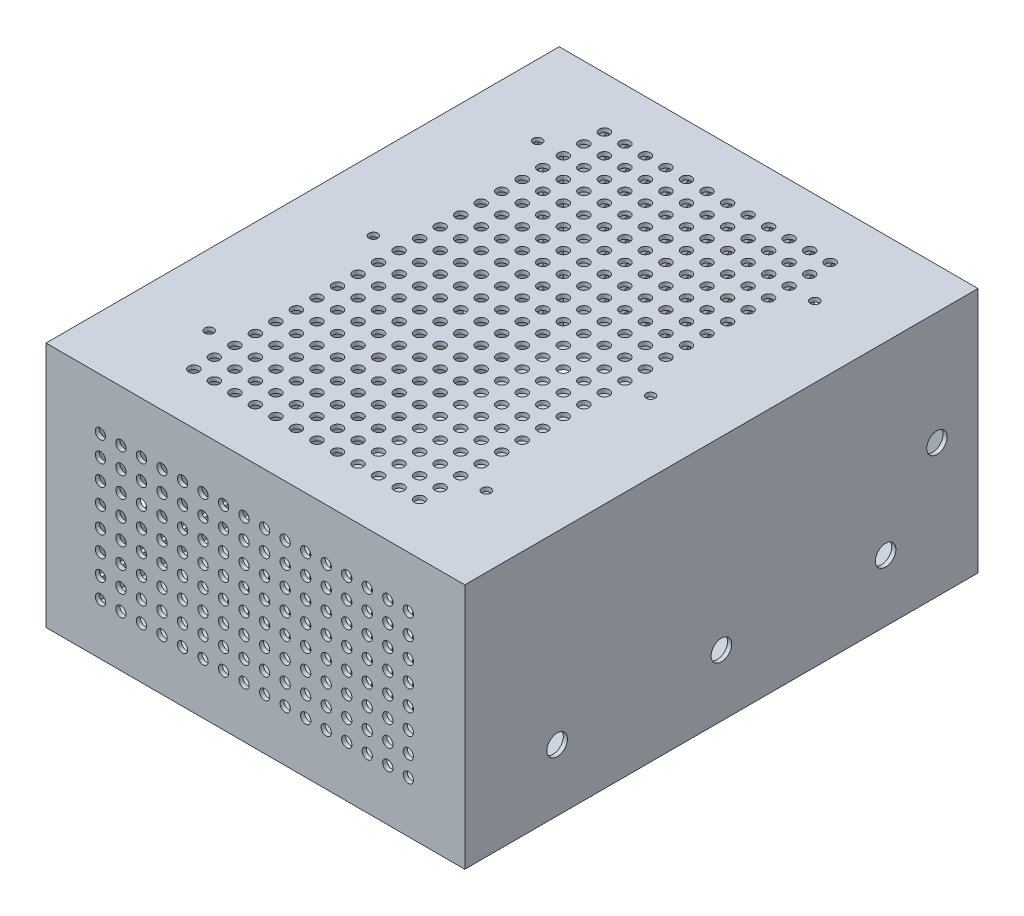
SolidWorks part; units mm, degrees
ref_plane "Alzado" through (0, 0, 0) normal (0, 0, 1) x (1, 0, 0)
ref_plane "Planta" through (0, 0, 0) normal (0, 1, 0) x (1, 0, 0)
ref_plane "Vista lateral" through (0, 0, 0) normal (1, 0, 0) x (0, 0, -1)
sketch "Croquis1" plane through (0, 0, 0) normal (0, 0, 1) x (1, 0, 0)
  line L0 (-100, 0) -> (100, 0)
  line L1 (100, 0) -> (100, 116)
  line L2 (100, 116) -> (-100, 116)
  line L3 (-100, 116) -> (-100, 0)
  line L4 (-80, 96) -> (-80, 20)
  line L5 (-80, 20) -> (80, 20)
  line L6 (80, 20) -> (80, 96)
  line L7 (80, 96) -> (-80, 96)
  point P3 (0, 0)
  dimension "D1" = 116
  dimension "D2" = 200
  dimension "D3" = 20
  dimension "D4" = 20
  dimension "D5" = 20
  dimension "D6" = 20
extrude "Saliente-Extruir1" add sketch "Croquis1" against normal blind 2
sketch "Croquis2" plane through (0, 0, 0) normal (0, 0, 1) x (1, 0, 0)
  line L0 (-80, 96) -> (-80, 20)
  line L1 (-80, 20) -> (80, 20)
  line L3 (80, 20) -> (80, 96)
  line L4 (80, 96) -> (-80, 96)
  circle A0 centre (-75.5, 93) radius 2.5
  circle A1 centre (-65.5, 93) radius 2.5
  circle A2 centre (-55.5, 93) radius 2.5
  circle A3 centre (-45.5, 93) radius 2.5
  circle A4 centre (-35.5, 93) radius 2.5
  circle A5 centre (-25.5, 93) radius 2.5
  circle A6 centre (-15.5, 93) radius 2.5
  circle A7 centre (-5.5, 93) radius 2.5
  circle A8 centre (4.5, 93) radius 2.5
  circle A9 centre (14.5, 93) radius 2.5
  circle A10 centre (24.5, 93) radius 2.5
  circle A11 centre (34.5, 93) radius 2.5
  circle A12 centre (44.5, 93) radius 2.5
  circle A13 centre (54.5, 93) radius 2.5
  circle A14 centre (64.5, 93) radius 2.5
  circle A15 centre (74.5, 93) radius 2.5
  circle A16 centre (-65.5, 83) radius 2.5
  circle A17 centre (-55.5, 83) radius 2.5
  circle A18 centre (-45.5, 83) radius 2.5
  circle A19 centre (-35.5, 83) radius 2.5
  circle A20 centre (-25.5, 83) radius 2.5
  circle A21 centre (-15.5, 83) radius 2.5
  circle A22 centre (-5.5, 83) radius 2.5
  circle A23 centre (4.5, 83) radius 2.5
  circle A24 centre (14.5, 83) radius 2.5
  circle A25 centre (24.5, 83) radius 2.5
  circle A26 centre (34.5, 83) radius 2.5
  circle A27 centre (44.5, 83) radius 2.5
  circle A28 centre (54.5, 83) radius 2.5
  circle A29 centre (64.5, 83) radius 2.5
  circle A30 centre (74.5, 83) radius 2.5
  circle A31 centre (-65.5, 73) radius 2.5
  circle A32 centre (-55.5, 73) radius 2.5
  circle A33 centre (-45.5, 73) radius 2.5
  circle A34 centre (-35.5, 73) radius 2.5
  circle A35 centre (-25.5, 73) radius 2.5
  circle A36 centre (-15.5, 73) radius 2.5
  circle A37 centre (-5.5, 73) radius 2.5
  circle A38 centre (4.5, 73) radius 2.5
  circle A39 centre (14.5, 73) radius 2.5
  circle A40 centre (24.5, 73) radius 2.5
  circle A41 centre (34.5, 73) radius 2.5
  circle A42 centre (44.5, 73) radius 2.5
  circle A43 centre (54.5, 73) radius 2.5
  circle A44 centre (64.5, 73) radius 2.5
  circle A45 centre (74.5, 73) radius 2.5
  circle A46 centre (-65.5, 63) radius 2.5
  circle A47 centre (-55.5, 63) radius 2.5
  circle A48 centre (-45.5, 63) radius 2.5
  circle A49 centre (-35.5, 63) radius 2.5
  circle A50 centre (-25.5, 63) radius 2.5
  circle A51 centre (-15.5, 63) radius 2.5
  circle A52 centre (-5.5, 63) radius 2.5
  circle A53 centre (4.5, 63) radius 2.5
  circle A54 centre (14.5, 63) radius 2.5
  circle A55 centre (24.5, 63) radius 2.5
  circle A56 centre (34.5, 63) radius 2.5
  circle A57 centre (44.5, 63) radius 2.5
  circle A58 centre (54.5, 63) radius 2.5
  circle A59 centre (64.5, 63) radius 2.5
  circle A60 centre (74.5, 63) radius 2.5
  circle A61 centre (-65.5, 53) radius 2.5
  circle A62 centre (-55.5, 53) radius 2.5
  circle A63 centre (-45.5, 53) radius 2.5
  circle A64 centre (-35.5, 53) radius 2.5
  circle A65 centre (-25.5, 53) radius 2.5
  circle A66 centre (-15.5, 53) radius 2.5
  circle A67 centre (-5.5, 53) radius 2.5
  circle A68 centre (4.5, 53) radius 2.5
  circle A69 centre (14.5, 53) radius 2.5
  circle A70 centre (24.5, 53) radius 2.5
  circle A71 centre (34.5, 53) radius 2.5
  circle A72 centre (44.5, 53) radius 2.5
  circle A73 centre (54.5, 53) radius 2.5
  circle A74 centre (64.5, 53) radius 2.5
  circle A75 centre (74.5, 53) radius 2.5
  circle A76 centre (-65.5, 43) radius 2.5
  circle A77 centre (-55.5, 43) radius 2.5
  circle A78 centre (-45.5, 43) radius 2.5
  circle A79 centre (-35.5, 43) radius 2.5
  circle A80 centre (-25.5, 43) radius 2.5
  circle A81 centre (-15.5, 43) radius 2.5
  circle A82 centre (-5.5, 43) radius 2.5
  circle A83 centre (4.5, 43) radius 2.5
  circle A84 centre (14.5, 43) radius 2.5
  circle A85 centre (24.5, 43) radius 2.5
  circle A86 centre (34.5, 43) radius 2.5
  circle A87 centre (44.5, 43) radius 2.5
  circle A88 centre (54.5, 43) radius 2.5
  circle A89 centre (64.5, 43) radius 2.5
  circle A90 centre (74.5, 43) radius 2.5
  circle A91 centre (-65.5, 33) radius 2.5
  circle A92 centre (-55.5, 33) radius 2.5
  circle A93 centre (-45.5, 33) radius 2.5
  circle A94 centre (-35.5, 33) radius 2.5
  circle A95 centre (-25.5, 33) radius 2.5
  circle A96 centre (-15.5, 33) radius 2.5
  circle A97 centre (-5.5, 33) radius 2.5
  circle A98 centre (4.5, 33) radius 2.5
  circle A99 centre (14.5, 33) radius 2.5
  circle A100 centre (24.5, 33) radius 2.5
  circle A101 centre (34.5, 33) radius 2.5
  circle A102 centre (44.5, 33) radius 2.5
  circle A103 centre (54.5, 33) radius 2.5
  circle A104 centre (64.5, 33) radius 2.5
  circle A105 centre (74.5, 33) radius 2.5
  circle A106 centre (-65.5, 23) radius 2.5
  circle A107 centre (-55.5, 23) radius 2.5
  circle A108 centre (-45.5, 23) radius 2.5
  circle A109 centre (-35.5, 23) radius 2.5
  circle A110 centre (-25.5, 23) radius 2.5
  circle A111 centre (-15.5, 23) radius 2.5
  circle A112 centre (-5.5, 23) radius 2.5
  circle A113 centre (4.5, 23) radius 2.5
  circle A114 centre (14.5, 23) radius 2.5
  circle A115 centre (24.5, 23) radius 2.5
  circle A116 centre (34.5, 23) radius 2.5
  circle A117 centre (44.5, 23) radius 2.5
  circle A118 centre (54.5, 23) radius 2.5
  circle A119 centre (64.5, 23) radius 2.5
  circle A120 centre (74.5, 23) radius 2.5
  circle A121 centre (-75.5, 83) radius 2.5
  circle A122 centre (-75.5, 73) radius 2.5
  circle A123 centre (-75.5, 63) radius 2.5
  circle A124 centre (-75.5, 53) radius 2.5
  circle A125 centre (-75.5, 43) radius 2.5
  circle A126 centre (-75.5, 33) radius 2.5
  circle A127 centre (-75.5, 23) radius 2.5
  dimension "D1" = 5
  dimension "D2" = 3
  dimension "D3" = 4.5
  dimension "D4" = 16
  dimension "D5" = 8
extrude "Saliente-Extruir2" add sketch "Croquis2" against normal blind 2
sketch "Croquis3" plane through (0, 0, 0) normal (0, -1, 0) x (1, 0, 0)
  line L0 (-100, 0) -> (-100, -248)
  line L1 (100, 0) -> (100, -248)
  line L2 (100, -248) -> (-100, -248)
  line L3 (-100, 0) -> (100, 0)
  line L4 (-70, -50) -> (-70, -198)
  line L5 (-70, -198) -> (70, -198)
  line L6 (-70, -50) -> (70, -50)
  line L7 (70, -50) -> (70, -198)
  dimension "D1" = 248
  dimension "D2" = 50
  dimension "D3" = 50
  dimension "D4" = 30
  dimension "D5" = 30
extrude "Saliente-Extruir3" add sketch "Croquis3" along normal blind 2
sketch "Croquis4" plane through (0, -2, 0) normal (0, -1, 0) x (1, 0, 0)
  line L0 (-70, -50) -> (-70, -198)
  line L1 (-70, -198) -> (70, -198)
  line L2 (70, -198) -> (70, -50)
  line L3 (70, -50) -> (-70, -50)
  circle A0 centre (-65, -55) radius 2.5
  circle A1 centre (-55, -55) radius 2.5
  circle A2 centre (-45, -55) radius 2.5
  circle A3 centre (-35, -55) radius 2.5
  circle A4 centre (-25, -55) radius 2.5
  circle A5 centre (-15, -55) radius 2.5
  circle A6 centre (-5, -55) radius 2.5
  circle A7 centre (5, -55) radius 2.5
  circle A8 centre (15, -55) radius 2.5
  circle A9 centre (25, -55) radius 2.5
  circle A10 centre (35, -55) radius 2.5
  circle A11 centre (45, -55) radius 2.5
  circle A12 centre (55, -55) radius 2.5
  circle A13 centre (65, -55) radius 2.5
  circle A14 centre (-55, -65) radius 2.5
  circle A15 centre (-45, -65) radius 2.5
  circle A16 centre (-35, -65) radius 2.5
  circle A17 centre (-25, -65) radius 2.5
  circle A18 centre (-15, -65) radius 2.5
  circle A19 centre (-5, -65) radius 2.5
  circle A20 centre (5, -65) radius 2.5
  circle A21 centre (15, -65) radius 2.5
  circle A22 centre (25, -65) radius 2.5
  circle A23 centre (35, -65) radius 2.5
  circle A24 centre (45, -65) radius 2.5
  circle A25 centre (55, -65) radius 2.5
  circle A26 centre (65, -65) radius 2.5
  circle A27 centre (-55, -75) radius 2.5
  circle A28 centre (-45, -75) radius 2.5
  circle A29 centre (-35, -75) radius 2.5
  circle A30 centre (-25, -75) radius 2.5
  circle A31 centre (-15, -75) radius 2.5
  circle A32 centre (-5, -75) radius 2.5
  circle A33 centre (5, -75) radius 2.5
  circle A34 centre (15, -75) radius 2.5
  circle A35 centre (25, -75) radius 2.5
  circle A36 centre (35, -75) radius 2.5
  circle A37 centre (45, -75) radius 2.5
  circle A38 centre (55, -75) radius 2.5
  circle A39 centre (65, -75) radius 2.5
  circle A40 centre (-55, -85) radius 2.5
  circle A41 centre (-45, -85) radius 2.5
  circle A42 centre (-35, -85) radius 2.5
  circle A43 centre (-25, -85) radius 2.5
  circle A44 centre (-15, -85) radius 2.5
  circle A45 centre (-5, -85) radius 2.5
  circle A46 centre (5, -85) radius 2.5
  circle A47 centre (15, -85) radius 2.5
  circle A48 centre (25, -85) radius 2.5
  circle A49 centre (35, -85) radius 2.5
  circle A50 centre (45, -85) radius 2.5
  circle A51 centre (55, -85) radius 2.5
  circle A52 centre (65, -85) radius 2.5
  circle A53 centre (-55, -95) radius 2.5
  circle A54 centre (-45, -95) radius 2.5
  circle A55 centre (-35, -95) radius 2.5
  circle A56 centre (-25, -95) radius 2.5
  circle A57 centre (-15, -95) radius 2.5
  circle A58 centre (-5, -95) radius 2.5
  circle A59 centre (5, -95) radius 2.5
  circle A60 centre (15, -95) radius 2.5
  circle A61 centre (25, -95) radius 2.5
  circle A62 centre (35, -95) radius 2.5
  circle A63 centre (45, -95) radius 2.5
  circle A64 centre (55, -95) radius 2.5
  circle A65 centre (65, -95) radius 2.5
  circle A66 centre (-55, -105) radius 2.5
  circle A67 centre (-45, -105) radius 2.5
  circle A68 centre (-35, -105) radius 2.5
  circle A69 centre (-25, -105) radius 2.5
  circle A70 centre (-15, -105) radius 2.5
  circle A71 centre (-5, -105) radius 2.5
  circle A72 centre (5, -105) radius 2.5
  circle A73 centre (15, -105) radius 2.5
  circle A74 centre (25, -105) radius 2.5
  circle A75 centre (35, -105) radius 2.5
  circle A76 centre (45, -105) radius 2.5
  circle A77 centre (55, -105) radius 2.5
  circle A78 centre (65, -105) radius 2.5
  circle A79 centre (-55, -115) radius 2.5
  circle A80 centre (-45, -115) radius 2.5
  circle A81 centre (-35, -115) radius 2.5
  circle A82 centre (-25, -115) radius 2.5
  circle A83 centre (-15, -115) radius 2.5
  circle A84 centre (-5, -115) radius 2.5
  circle A85 centre (5, -115) radius 2.5
  circle A86 centre (15, -115) radius 2.5
  circle A87 centre (25, -115) radius 2.5
  circle A88 centre (35, -115) radius 2.5
  circle A89 centre (45, -115) radius 2.5
  circle A90 centre (55, -115) radius 2.5
  circle A91 centre (65, -115) radius 2.5
  circle A92 centre (-55, -125) radius 2.5
  circle A93 centre (-45, -125) radius 2.5
  circle A94 centre (-35, -125) radius 2.5
  circle A95 centre (-25, -125) radius 2.5
  circle A96 centre (-15, -125) radius 2.5
  circle A97 centre (-5, -125) radius 2.5
  circle A98 centre (5, -125) radius 2.5
  circle A99 centre (15, -125) radius 2.5
  circle A100 centre (25, -125) radius 2.5
  circle A101 centre (35, -125) radius 2.5
  circle A102 centre (45, -125) radius 2.5
  circle A103 centre (55, -125) radius 2.5
  circle A104 centre (65, -125) radius 2.5
  circle A105 centre (-55, -135) radius 2.5
  circle A106 centre (-45, -135) radius 2.5
  circle A107 centre (-35, -135) radius 2.5
  circle A108 centre (-25, -135) radius 2.5
  circle A109 centre (-15, -135) radius 2.5
  circle A110 centre (-5, -135) radius 2.5
  circle A111 centre (5, -135) radius 2.5
  circle A112 centre (15, -135) radius 2.5
  circle A113 centre (25, -135) radius 2.5
  circle A114 centre (35, -135) radius 2.5
  circle A115 centre (45, -135) radius 2.5
  circle A116 centre (55, -135) radius 2.5
  circle A117 centre (65, -135) radius 2.5
  circle A118 centre (-55, -145) radius 2.5
  circle A119 centre (-45, -145) radius 2.5
  circle A120 centre (-35, -145) radius 2.5
  circle A121 centre (-25, -145) radius 2.5
  circle A122 centre (-15, -145) radius 2.5
  circle A123 centre (-5, -145) radius 2.5
  circle A124 centre (5, -145) radius 2.5
  circle A125 centre (15, -145) radius 2.5
  circle A126 centre (25, -145) radius 2.5
  circle A127 centre (35, -145) radius 2.5
  circle A128 centre (45, -145) radius 2.5
  circle A129 centre (55, -145) radius 2.5
  circle A130 centre (65, -145) radius 2.5
  circle A131 centre (-55, -155) radius 2.5
  circle A132 centre (-45, -155) radius 2.5
  circle A133 centre (-35, -155) radius 2.5
  circle A134 centre (-25, -155) radius 2.5
  circle A135 centre (-15, -155) radius 2.5
  circle A136 centre (-5, -155) radius 2.5
  circle A137 centre (5, -155) radius 2.5
  circle A138 centre (15, -155) radius 2.5
  circle A139 centre (25, -155) radius 2.5
  circle A140 centre (35, -155) radius 2.5
  circle A141 centre (45, -155) radius 2.5
  circle A142 centre (55, -155) radius 2.5
  circle A143 centre (65, -155) radius 2.5
  circle A144 centre (-55, -165) radius 2.5
  circle A145 centre (-45, -165) radius 2.5
  circle A146 centre (-35, -165) radius 2.5
  circle A147 centre (-25, -165) radius 2.5
  circle A148 centre (-15, -165) radius 2.5
  circle A149 centre (-5, -165) radius 2.5
  circle A150 centre (5, -165) radius 2.5
  circle A151 centre (15, -165) radius 2.5
  circle A152 centre (25, -165) radius 2.5
  circle A153 centre (35, -165) radius 2.5
  circle A154 centre (45, -165) radius 2.5
  circle A155 centre (55, -165) radius 2.5
  circle A156 centre (65, -165) radius 2.5
  circle A157 centre (-55, -175) radius 2.5
  circle A158 centre (-45, -175) radius 2.5
  circle A159 centre (-35, -175) radius 2.5
  circle A160 centre (-25, -175) radius 2.5
  circle A161 centre (-15, -175) radius 2.5
  circle A162 centre (-5, -175) radius 2.5
  circle A163 centre (5, -175) radius 2.5
  circle A164 centre (15, -175) radius 2.5
  circle A165 centre (25, -175) radius 2.5
  circle A166 centre (35, -175) radius 2.5
  circle A167 centre (45, -175) radius 2.5
  circle A168 centre (55, -175) radius 2.5
  circle A169 centre (65, -175) radius 2.5
  circle A170 centre (-55, -185) radius 2.5
  circle A171 centre (-45, -185) radius 2.5
  circle A172 centre (-35, -185) radius 2.5
  circle A173 centre (-25, -185) radius 2.5
  circle A174 centre (-15, -185) radius 2.5
  circle A175 centre (-5, -185) radius 2.5
  circle A176 centre (5, -185) radius 2.5
  circle A177 centre (15, -185) radius 2.5
  circle A178 centre (25, -185) radius 2.5
  circle A179 centre (35, -185) radius 2.5
  circle A180 centre (45, -185) radius 2.5
  circle A181 centre (55, -185) radius 2.5
  circle A182 centre (65, -185) radius 2.5
  circle A183 centre (-55, -195) radius 2.5
  circle A184 centre (-45, -195) radius 2.5
  circle A185 centre (-35, -195) radius 2.5
  circle A186 centre (-25, -195) radius 2.5
  circle A187 centre (-15, -195) radius 2.5
  circle A188 centre (-5, -195) radius 2.5
  circle A189 centre (5, -195) radius 2.5
  circle A190 centre (15, -195) radius 2.5
  circle A191 centre (25, -195) radius 2.5
  circle A192 centre (35, -195) radius 2.5
  circle A193 centre (45, -195) radius 2.5
  circle A194 centre (55, -195) radius 2.5
  circle A195 centre (65, -195) radius 2.5
  circle A196 centre (-65, -65) radius 2.5
  circle A197 centre (-65, -75) radius 2.5
  circle A198 centre (-65, -85) radius 2.5
  circle A199 centre (-65, -95) radius 2.5
  circle A200 centre (-65, -105) radius 2.5
  circle A201 centre (-65, -115) radius 2.5
  circle A202 centre (-65, -125) radius 2.5
  circle A203 centre (-65, -135) radius 2.5
  circle A204 centre (-65, -145) radius 2.5
  circle A205 centre (-65, -155) radius 2.5
  circle A206 centre (-65, -165) radius 2.5
  circle A207 centre (-65, -175) radius 2.5
  circle A208 centre (-65, -185) radius 2.5
  circle A209 centre (-65, -195) radius 2.5
  dimension "D1" = 5
  dimension "D2" = 5
  dimension "D3" = 5
  dimension "D4" = 14
  dimension "D5" = 15
extrude "Saliente-Extruir4" add sketch "Croquis4" against normal blind 2
sketch "Croquis5" plane through (0, 0, -248) normal (0, 0, -1) x (-1, 0, 0)
  line L0 (-100, -2) -> (-100, 116)
  line L1 (-100, 116) -> (100, 116)
  line L2 (100, 116) -> (100, -2)
  line L3 (100, -2) -> (-100, -2)
  line L4 (-80, 96) -> (-80, 18) construction
  line L5 (-80, 18) -> (80, 18) construction
  line L6 (80, 18) -> (80, 96) construction
  line L7 (-80, 96) -> (80, 96) construction
  circle A0 centre (-74.5, 93) radius 2.5
  circle A1 centre (-64.5, 93) radius 2.5
  circle A2 centre (-54.5, 93) radius 2.5
  circle A3 centre (-44.5, 93) radius 2.5
  circle A4 centre (-34.5, 93) radius 2.5
  circle A5 centre (-24.5, 93) radius 2.5
  circle A6 centre (-14.5, 93) radius 2.5
  circle A7 centre (-4.5, 93) radius 2.5
  circle A8 centre (5.5, 93) radius 2.5
  circle A9 centre (15.5, 93) radius 2.5
  circle A10 centre (25.5, 93) radius 2.5
  circle A11 centre (35.5, 93) radius 2.5
  circle A12 centre (45.5, 93) radius 2.5
  circle A13 centre (55.5, 93) radius 2.5
  circle A14 centre (65.5, 93) radius 2.5
  circle A15 centre (75.5, 93) radius 2.5
  circle A16 centre (-64.5, 83) radius 2.5
  circle A17 centre (-54.5, 83) radius 2.5
  circle A18 centre (-44.5, 83) radius 2.5
  circle A19 centre (-34.5, 83) radius 2.5
  circle A20 centre (-24.5, 83) radius 2.5
  circle A21 centre (-14.5, 83) radius 2.5
  circle A22 centre (-4.5, 83) radius 2.5
  circle A23 centre (5.5, 83) radius 2.5
  circle A24 centre (15.5, 83) radius 2.5
  circle A25 centre (25.5, 83) radius 2.5
  circle A26 centre (35.5, 83) radius 2.5
  circle A27 centre (45.5, 83) radius 2.5
  circle A28 centre (55.5, 83) radius 2.5
  circle A29 centre (65.5, 83) radius 2.5
  circle A30 centre (75.5, 83) radius 2.5
  circle A31 centre (-64.5, 73) radius 2.5
  circle A32 centre (-54.5, 73) radius 2.5
  circle A33 centre (-44.5, 73) radius 2.5
  circle A34 centre (-34.5, 73) radius 2.5
  circle A35 centre (-24.5, 73) radius 2.5
  circle A36 centre (-14.5, 73) radius 2.5
  circle A37 centre (-4.5, 73) radius 2.5
  circle A38 centre (5.5, 73) radius 2.5
  circle A39 centre (15.5, 73) radius 2.5
  circle A40 centre (25.5, 73) radius 2.5
  circle A41 centre (35.5, 73) radius 2.5
  circle A42 centre (45.5, 73) radius 2.5
  circle A43 centre (55.5, 73) radius 2.5
  circle A44 centre (65.5, 73) radius 2.5
  circle A45 centre (75.5, 73) radius 2.5
  circle A46 centre (-64.5, 63) radius 2.5
  circle A47 centre (-54.5, 63) radius 2.5
  circle A48 centre (-44.5, 63) radius 2.5
  circle A49 centre (-34.5, 63) radius 2.5
  circle A50 centre (-24.5, 63) radius 2.5
  circle A51 centre (-14.5, 63) radius 2.5
  circle A52 centre (-4.5, 63) radius 2.5
  circle A53 centre (5.5, 63) radius 2.5
  circle A54 centre (15.5, 63) radius 2.5
  circle A55 centre (25.5, 63) radius 2.5
  circle A56 centre (35.5, 63) radius 2.5
  circle A57 centre (45.5, 63) radius 2.5
  circle A58 centre (55.5, 63) radius 2.5
  circle A59 centre (65.5, 63) radius 2.5
  circle A60 centre (75.5, 63) radius 2.5
  circle A61 centre (-64.5, 53) radius 2.5
  circle A62 centre (-54.5, 53) radius 2.5
  circle A63 centre (-44.5, 53) radius 2.5
  circle A64 centre (-34.5, 53) radius 2.5
  circle A65 centre (-24.5, 53) radius 2.5
  circle A66 centre (-14.5, 53) radius 2.5
  circle A67 centre (-4.5, 53) radius 2.5
  circle A68 centre (5.5, 53) radius 2.5
  circle A69 centre (15.5, 53) radius 2.5
  circle A70 centre (25.5, 53) radius 2.5
  circle A71 centre (35.5, 53) radius 2.5
  circle A72 centre (45.5, 53) radius 2.5
  circle A73 centre (55.5, 53) radius 2.5
  circle A74 centre (65.5, 53) radius 2.5
  circle A75 centre (75.5, 53) radius 2.5
  circle A76 centre (-64.5, 43) radius 2.5
  circle A77 centre (-54.5, 43) radius 2.5
  circle A78 centre (-44.5, 43) radius 2.5
  circle A79 centre (-34.5, 43) radius 2.5
  circle A80 centre (-24.5, 43) radius 2.5
  circle A81 centre (-14.5, 43) radius 2.5
  circle A82 centre (-4.5, 43) radius 2.5
  circle A83 centre (5.5, 43) radius 2.5
  circle A84 centre (15.5, 43) radius 2.5
  circle A85 centre (25.5, 43) radius 2.5
  circle A86 centre (35.5, 43) radius 2.5
  circle A87 centre (45.5, 43) radius 2.5
  circle A88 centre (55.5, 43) radius 2.5
  circle A89 centre (65.5, 43) radius 2.5
  circle A90 centre (75.5, 43) radius 2.5
  circle A91 centre (-64.5, 33) radius 2.5
  circle A92 centre (-54.5, 33) radius 2.5
  circle A93 centre (-44.5, 33) radius 2.5
  circle A94 centre (-34.5, 33) radius 2.5
  circle A95 centre (-24.5, 33) radius 2.5
  circle A96 centre (-14.5, 33) radius 2.5
  circle A97 centre (-4.5, 33) radius 2.5
  circle A98 centre (5.5, 33) radius 2.5
  circle A99 centre (15.5, 33) radius 2.5
  circle A100 centre (25.5, 33) radius 2.5
  circle A101 centre (35.5, 33) radius 2.5
  circle A102 centre (45.5, 33) radius 2.5
  circle A103 centre (55.5, 33) radius 2.5
  circle A104 centre (65.5, 33) radius 2.5
  circle A105 centre (75.5, 33) radius 2.5
  circle A106 centre (-64.5, 23) radius 2.5
  circle A107 centre (-54.5, 23) radius 2.5
  circle A108 centre (-44.5, 23) radius 2.5
  circle A109 centre (-34.5, 23) radius 2.5
  circle A110 centre (-24.5, 23) radius 2.5
  circle A111 centre (-14.5, 23) radius 2.5
  circle A112 centre (-4.5, 23) radius 2.5
  circle A113 centre (5.5, 23) radius 2.5
  circle A114 centre (15.5, 23) radius 2.5
  circle A115 centre (25.5, 23) radius 2.5
  circle A116 centre (35.5, 23) radius 2.5
  circle A117 centre (45.5, 23) radius 2.5
  circle A118 centre (55.5, 23) radius 2.5
  circle A119 centre (65.5, 23) radius 2.5
  circle A120 centre (75.5, 23) radius 2.5
  circle A121 centre (-74.5, 83) radius 2.5
  circle A122 centre (-74.5, 73) radius 2.5
  circle A123 centre (-74.5, 63) radius 2.5
  circle A124 centre (-74.5, 53) radius 2.5
  circle A125 centre (-74.5, 43) radius 2.5
  circle A126 centre (-74.5, 33) radius 2.5
  circle A127 centre (-74.5, 23) radius 2.5
  dimension "D5" = 5
  dimension "D1" = 20
  dimension "D2" = 20
  dimension "D3" = 20
  dimension "D4" = 20
  dimension "D6" = 16
  dimension "D7" = 8
extrude "Saliente-Extruir5" add sketch "Croquis5" along normal blind 2
sketch "Croquis7" plane through (100, 0, 0) normal (1, 0, 0) x (0, 0, -1)
  line L0 (0, 116) -> (0, -2)
  line L1 (0, -2) -> (250, -2)
  line L2 (250, -2) -> (250, 116)
  line L3 (250, 116) -> (0, 116)
  line L4 (0, 28) -> (250, 28) construction
  line L5 (125, -2) -> (125, 116) construction
  circle A0 centre (45, 28) radius 5
  circle A1 centre (125, 28) radius 5
  circle A2 centre (205, 28) radius 5
  dimension "D3" = 10
  dimension "D1" = 80
  dimension "D2" = 80
  dimension "D4" = 30
extrude "Saliente-Extruir6" add sketch "Croquis7" along normal blind 2
sketch "Croquis9" plane through (-100, 0, 0) normal (-1, 0, 0) x (0, 0, 1)
  line L1 (-250, -2) -> (0, -2)
  line L4 (-250, 28) -> (0, 28) construction
  line L5 (-125, 118) -> (-125, -2) construction
  line L8 (-250, 116) -> (0, 116)
  line L9 (-250, 116) -> (-250, -2)
  line L10 (0, -2) -> (0, 116)
  circle A0 centre (-125, 28) radius 5
  circle A1 centre (-45, 28) radius 5
  circle A2 centre (-205, 28) radius 5
  circle A3 centre (-205, 28) radius 5 construction
  dimension "D3" = 10
  dimension "D1" = 80
  dimension "D2" = 80
extrude "Saliente-Extruir8" add sketch "Croquis9" along normal blind 2
sketch "Croquis10" plane through (0, 116, 0) normal (0, 1, 0) x (1, 0, 0)
  line L0 (-102, 250) -> (-102, 0)
  line L1 (-102, 0) -> (102, 0)
  line L2 (102, 0) -> (102, 250)
  line L3 (102, 250) -> (-102, 250)
  line L8 (-62, 230) -> (-62, 20)
  line L9 (-62, 20) -> (62, 20)
  line L10 (62, 20) -> (62, 230)
  line L11 (-62, 230) -> (62, 230)
  dimension "D1" = 40
  dimension "D2" = 40
  dimension "D3" = 20
  dimension "D4" = 20
  dimension "D8" = 1
extrude "Saliente-Extruir11" add sketch "Croquis10" along normal blind 2
sketch "Croquis11" plane through (0, 118, 0) normal (0, 1, 0) x (1, 0, 0)
  line L0 (-62, 230) -> (-62, 20)
  line L1 (-62, 20) -> (62, 20)
  line L2 (-62, 230) -> (62, 230)
  line L3 (62, 230) -> (62, 20)
  circle A0 centre (-55, 225) radius 2.5
  circle A1 centre (-45, 225) radius 2.5
  circle A2 centre (-35, 225) radius 2.5
  circle A3 centre (-25, 225) radius 2.5
  circle A4 centre (-15, 225) radius 2.5
  circle A5 centre (-5, 225) radius 2.5
  circle A6 centre (5, 225) radius 2.5
  circle A7 centre (15, 225) radius 2.5
  circle A8 centre (25, 225) radius 2.5
  circle A9 centre (35, 225) radius 2.5
  circle A10 centre (45, 225) radius 2.5
  circle A11 centre (55, 225) radius 2.5
  circle A12 centre (-45, 215) radius 2.5
  circle A13 centre (-35, 215) radius 2.5
  circle A14 centre (-25, 215) radius 2.5
  circle A15 centre (-15, 215) radius 2.5
  circle A16 centre (-5, 215) radius 2.5
  circle A17 centre (5, 215) radius 2.5
  circle A18 centre (15, 215) radius 2.5
  circle A19 centre (25, 215) radius 2.5
  circle A20 centre (35, 215) radius 2.5
  circle A21 centre (45, 215) radius 2.5
  circle A22 centre (55, 215) radius 2.5
  circle A23 centre (-45, 205) radius 2.5
  circle A24 centre (-35, 205) radius 2.5
  circle A25 centre (-25, 205) radius 2.5
  circle A26 centre (-15, 205) radius 2.5
  circle A27 centre (-5, 205) radius 2.5
  circle A28 centre (5, 205) radius 2.5
  circle A29 centre (15, 205) radius 2.5
  circle A30 centre (25, 205) radius 2.5
  circle A31 centre (35, 205) radius 2.5
  circle A32 centre (45, 205) radius 2.5
  circle A33 centre (55, 205) radius 2.5
  circle A34 centre (-45, 195) radius 2.5
  circle A35 centre (-35, 195) radius 2.5
  circle A36 centre (-25, 195) radius 2.5
  circle A37 centre (-15, 195) radius 2.5
  circle A38 centre (-5, 195) radius 2.5
  circle A39 centre (5, 195) radius 2.5
  circle A40 centre (15, 195) radius 2.5
  circle A41 centre (25, 195) radius 2.5
  circle A42 centre (35, 195) radius 2.5
  circle A43 centre (45, 195) radius 2.5
  circle A44 centre (55, 195) radius 2.5
  circle A45 centre (-45, 185) radius 2.5
  circle A46 centre (-35, 185) radius 2.5
  circle A47 centre (-25, 185) radius 2.5
  circle A48 centre (-15, 185) radius 2.5
  circle A49 centre (-5, 185) radius 2.5
  circle A50 centre (5, 185) radius 2.5
  circle A51 centre (15, 185) radius 2.5
  circle A52 centre (25, 185) radius 2.5
  circle A53 centre (35, 185) radius 2.5
  circle A54 centre (45, 185) radius 2.5
  circle A55 centre (55, 185) radius 2.5
  circle A56 centre (-45, 175) radius 2.5
  circle A57 centre (-35, 175) radius 2.5
  circle A58 centre (-25, 175) radius 2.5
  circle A59 centre (-15, 175) radius 2.5
  circle A60 centre (-5, 175) radius 2.5
  circle A61 centre (5, 175) radius 2.5
  circle A62 centre (15, 175) radius 2.5
  circle A63 centre (25, 175) radius 2.5
  circle A64 centre (35, 175) radius 2.5
  circle A65 centre (45, 175) radius 2.5
  circle A66 centre (55, 175) radius 2.5
  circle A67 centre (-45, 165) radius 2.5
  circle A68 centre (-35, 165) radius 2.5
  circle A69 centre (-25, 165) radius 2.5
  circle A70 centre (-15, 165) radius 2.5
  circle A71 centre (-5, 165) radius 2.5
  circle A72 centre (5, 165) radius 2.5
  circle A73 centre (15, 165) radius 2.5
  circle A74 centre (25, 165) radius 2.5
  circle A75 centre (35, 165) radius 2.5
  circle A76 centre (45, 165) radius 2.5
  circle A77 centre (55, 165) radius 2.5
  circle A78 centre (-45, 155) radius 2.5
  circle A79 centre (-35, 155) radius 2.5
  circle A80 centre (-25, 155) radius 2.5
  circle A81 centre (-15, 155) radius 2.5
  circle A82 centre (-5, 155) radius 2.5
  circle A83 centre (5, 155) radius 2.5
  circle A84 centre (15, 155) radius 2.5
  circle A85 centre (25, 155) radius 2.5
  circle A86 centre (35, 155) radius 2.5
  circle A87 centre (45, 155) radius 2.5
  circle A88 centre (55, 155) radius 2.5
  circle A89 centre (-45, 145) radius 2.5
  circle A90 centre (-35, 145) radius 2.5
  circle A91 centre (-25, 145) radius 2.5
  circle A92 centre (-15, 145) radius 2.5
  circle A93 centre (-5, 145) radius 2.5
  circle A94 centre (5, 145) radius 2.5
  circle A95 centre (15, 145) radius 2.5
  circle A96 centre (25, 145) radius 2.5
  circle A97 centre (35, 145) radius 2.5
  circle A98 centre (45, 145) radius 2.5
  circle A99 centre (55, 145) radius 2.5
  circle A100 centre (-45, 135) radius 2.5
  circle A101 centre (-35, 135) radius 2.5
  circle A102 centre (-25, 135) radius 2.5
  circle A103 centre (-15, 135) radius 2.5
  circle A104 centre (-5, 135) radius 2.5
  circle A105 centre (5, 135) radius 2.5
  circle A106 centre (15, 135) radius 2.5
  circle A107 centre (25, 135) radius 2.5
  circle A108 centre (35, 135) radius 2.5
  circle A109 centre (45, 135) radius 2.5
  circle A110 centre (55, 135) radius 2.5
  circle A111 centre (-45, 125) radius 2.5
  circle A112 centre (-35, 125) radius 2.5
  circle A113 centre (-25, 125) radius 2.5
  circle A114 centre (-15, 125) radius 2.5
  circle A115 centre (-5, 125) radius 2.5
  circle A116 centre (5, 125) radius 2.5
  circle A117 centre (15, 125) radius 2.5
  circle A118 centre (25, 125) radius 2.5
  circle A119 centre (35, 125) radius 2.5
  circle A120 centre (45, 125) radius 2.5
  circle A121 centre (55, 125) radius 2.5
  circle A122 centre (-45, 115) radius 2.5
  circle A123 centre (-35, 115) radius 2.5
  circle A124 centre (-25, 115) radius 2.5
  circle A125 centre (-15, 115) radius 2.5
  circle A126 centre (-5, 115) radius 2.5
  circle A127 centre (5, 115) radius 2.5
  circle A128 centre (15, 115) radius 2.5
  circle A129 centre (25, 115) radius 2.5
  circle A130 centre (35, 115) radius 2.5
  circle A131 centre (45, 115) radius 2.5
  circle A132 centre (55, 115) radius 2.5
  circle A133 centre (-45, 105) radius 2.5
  circle A134 centre (-35, 105) radius 2.5
  circle A135 centre (-25, 105) radius 2.5
  circle A136 centre (-15, 105) radius 2.5
  circle A137 centre (-5, 105) radius 2.5
  circle A138 centre (5, 105) radius 2.5
  circle A139 centre (15, 105) radius 2.5
  circle A140 centre (25, 105) radius 2.5
  circle A141 centre (35, 105) radius 2.5
  circle A142 centre (45, 105) radius 2.5
  circle A143 centre (55, 105) radius 2.5
  circle A144 centre (-45, 95) radius 2.5
  circle A145 centre (-35, 95) radius 2.5
  circle A146 centre (-25, 95) radius 2.5
  circle A147 centre (-15, 95) radius 2.5
  circle A148 centre (-5, 95) radius 2.5
  circle A149 centre (5, 95) radius 2.5
  circle A150 centre (15, 95) radius 2.5
  circle A151 centre (25, 95) radius 2.5
  circle A152 centre (35, 95) radius 2.5
  circle A153 centre (45, 95) radius 2.5
  circle A154 centre (55, 95) radius 2.5
  circle A155 centre (-45, 85) radius 2.5
  circle A156 centre (-35, 85) radius 2.5
  circle A157 centre (-25, 85) radius 2.5
  circle A158 centre (-15, 85) radius 2.5
  circle A159 centre (-5, 85) radius 2.5
  circle A160 centre (5, 85) radius 2.5
  circle A161 centre (15, 85) radius 2.5
  circle A162 centre (25, 85) radius 2.5
  circle A163 centre (35, 85) radius 2.5
  circle A164 centre (45, 85) radius 2.5
  circle A165 centre (55, 85) radius 2.5
  circle A166 centre (-45, 75) radius 2.5
  circle A167 centre (-35, 75) radius 2.5
  circle A168 centre (-25, 75) radius 2.5
  circle A169 centre (-15, 75) radius 2.5
  circle A170 centre (-5, 75) radius 2.5
  circle A171 centre (5, 75) radius 2.5
  circle A172 centre (15, 75) radius 2.5
  circle A173 centre (25, 75) radius 2.5
  circle A174 centre (35, 75) radius 2.5
  circle A175 centre (45, 75) radius 2.5
  circle A176 centre (55, 75) radius 2.5
  circle A177 centre (-45, 65) radius 2.5
  circle A178 centre (-35, 65) radius 2.5
  circle A179 centre (-25, 65) radius 2.5
  circle A180 centre (-15, 65) radius 2.5
  circle A181 centre (-5, 65) radius 2.5
  circle A182 centre (5, 65) radius 2.5
  circle A183 centre (15, 65) radius 2.5
  circle A184 centre (25, 65) radius 2.5
  circle A185 centre (35, 65) radius 2.5
  circle A186 centre (45, 65) radius 2.5
  circle A187 centre (55, 65) radius 2.5
  circle A188 centre (-45, 55) radius 2.5
  circle A189 centre (-35, 55) radius 2.5
  circle A190 centre (-25, 55) radius 2.5
  circle A191 centre (-15, 55) radius 2.5
  circle A192 centre (-5, 55) radius 2.5
  circle A193 centre (5, 55) radius 2.5
  circle A194 centre (15, 55) radius 2.5
  circle A195 centre (25, 55) radius 2.5
  circle A196 centre (35, 55) radius 2.5
  circle A197 centre (45, 55) radius 2.5
  circle A198 centre (55, 55) radius 2.5
  circle A199 centre (-45, 45) radius 2.5
  circle A200 centre (-35, 45) radius 2.5
  circle A201 centre (-25, 45) radius 2.5
  circle A202 centre (-15, 45) radius 2.5
  circle A203 centre (-5, 45) radius 2.5
  circle A204 centre (5, 45) radius 2.5
  circle A205 centre (15, 45) radius 2.5
  circle A206 centre (25, 45) radius 2.5
  circle A207 centre (35, 45) radius 2.5
  circle A208 centre (45, 45) radius 2.5
  circle A209 centre (55, 45) radius 2.5
  circle A210 centre (-45, 35) radius 2.5
  circle A211 centre (-35, 35) radius 2.5
  circle A212 centre (-25, 35) radius 2.5
  circle A213 centre (-15, 35) radius 2.5
  circle A214 centre (-5, 35) radius 2.5
  circle A215 centre (5, 35) radius 2.5
  circle A216 centre (15, 35) radius 2.5
  circle A217 centre (25, 35) radius 2.5
  circle A218 centre (35, 35) radius 2.5
  circle A219 centre (45, 35) radius 2.5
  circle A220 centre (55, 35) radius 2.5
  circle A221 centre (-45, 25) radius 2.5
  circle A222 centre (-35, 25) radius 2.5
  circle A223 centre (-25, 25) radius 2.5
  circle A224 centre (-15, 25) radius 2.5
  circle A225 centre (-5, 25) radius 2.5
  circle A226 centre (5, 25) radius 2.5
  circle A227 centre (15, 25) radius 2.5
  circle A228 centre (25, 25) radius 2.5
  circle A229 centre (35, 25) radius 2.5
  circle A230 centre (45, 25) radius 2.5
  circle A231 centre (55, 25) radius 2.5
  circle A232 centre (-55, 215) radius 2.5
  circle A233 centre (-55, 205) radius 2.5
  circle A234 centre (-55, 195) radius 2.5
  circle A235 centre (-55, 185) radius 2.5
  circle A236 centre (-55, 175) radius 2.5
  circle A237 centre (-55, 165) radius 2.5
  circle A238 centre (-55, 155) radius 2.5
  circle A239 centre (-55, 145) radius 2.5
  circle A240 centre (-55, 135) radius 2.5
  circle A241 centre (-55, 125) radius 2.5
  circle A242 centre (-55, 115) radius 2.5
  circle A243 centre (-55, 105) radius 2.5
  circle A244 centre (-55, 95) radius 2.5
  circle A245 centre (-55, 85) radius 2.5
  circle A246 centre (-55, 75) radius 2.5
  circle A247 centre (-55, 65) radius 2.5
  circle A248 centre (-55, 55) radius 2.5
  circle A249 centre (-55, 45) radius 2.5
  circle A250 centre (-55, 35) radius 2.5
  circle A251 centre (-55, 25) radius 2.5
  dimension "D3" = 5
  dimension "D1" = 5
  dimension "D2" = 7
  dimension "D4" = 12
extrude "Saliente-Extruir12" add sketch "Croquis11" against normal blind 2
sketch "Croquis12" plane through (102, 0, 0) normal (1, 0, 0) x (0, 0, -1)
  line L1 (250, -2) -> (250, 118) construction
  line L3 (0, 58) -> (250, 58) construction
  line L4 (0, 118) -> (0, -2) construction
  circle A1 centre (230, 63) radius 5
  dimension "D6" = 10
  dimension "D4" = 5
  dimension "D5" = 20
extrude "Cortar-Extruir1" cut sketch "Croquis12" against normal blind 5
sketch "Croquis13" plane through (0, 0, 0) normal (0, 1, 0) x (1, 0, 0)
  line L0 (-100, 248) -> (100, 248) construction
  line L1 (-100, 2) -> (-100, 248) construction
  line L2 (-85, 233) -> (100, 233) construction
  line L3 (100, 248) -> (100, 2) construction
  line L4 (-85, 233) -> (-85, 2) construction
  line L5 (-100, 2) -> (100, 2) construction
  line L6 (-85, 17) -> (85, 17) construction
  line L7 (85, 17) -> (85, 233) construction
  circle A0 centre (-85, 233) radius 4.5
  circle A1 centre (85, 233) radius 4.5
  circle A2 centre (85, 17) radius 4.5
  circle A3 centre (-85, 17) radius 4.5
  circle A4 centre (-85, 233) radius 25 construction
  dimension "D1" = 9
  dimension "D2" = 50
  dimension "D3" = 15
  dimension "D4" = 15
  dimension "D5" = 15
  dimension "D6" = 15
extrude "Cortar-Extruir2" cut sketch "Croquis13" against normal blind 10
sketch "Croquis14" plane through (0, 118, 0) normal (0, 1, 0) x (1, 0, 0)
  line L0 (102, 250) -> (-102, 250) construction
  line L1 (0, 250) -> (0, 0) construction
  line L2 (-102, 0) -> (102, 0) construction
  line L3 (-77.5, 227.5) -> (-77.5, 182.5) construction
  line L4 (-77.5, 182.5) -> (77.5, 182.5) construction
  line L5 (77.5, 182.5) -> (77.5, 227.5) construction
  line L6 (77.5, 227.5) -> (-77.5, 227.5) construction
  line L7 (-102, 250) -> (-102, 0) construction
  line L11 (-102, 125) -> (102, 125) construction
  line L12 (102, 0) -> (102, 250) construction
  line L13 (-77.5, 102.5) -> (77.5, 102.5) construction
  line L14 (-77.5, 147.5) -> (-77.5, 102.5) construction
  line L15 (77.5, 147.5) -> (-77.5, 147.5) construction
  line L16 (77.5, 102.5) -> (77.5, 147.5) construction
  line L17 (-77.5, 22.5) -> (77.5, 22.5) construction
  line L18 (-77.5, 67.5) -> (-77.5, 22.5) construction
  line L19 (77.5, 67.5) -> (-77.5, 67.5) construction
  line L20 (77.5, 22.5) -> (77.5, 67.5) construction
  line L21 (-77.5, 205) -> (77.5, 205) construction
  line L22 (-77.5, 45) -> (77.5, 45) construction
  circle A1 centre (-67.5, 205) radius 2.175
  circle A2 centre (67.5, 205) radius 2.175
  circle A3 centre (67.5, 125) radius 2.175
  circle A4 centre (-67.5, 125) radius 2.175
  circle A5 centre (-67.5, 45) radius 2.175
  circle A6 centre (67.5, 45) radius 2.175
  dimension "D6" = 4.35
  dimension "D7" = 10
  dimension "D8" = 10
  dimension "D1" = 45
  dimension "D2" = 155
  dimension "D3" = 22.5
  dimension "D4" = 24.5
  dimension "D5" = 3
extrude "Cortar-Extruir3" cut sketch "Croquis14" against normal blind 10
sketch "Croquis15" plane through (-100, 0, 0) normal (1, 0, 0) x (0, 0, -1)
  line L0 (2, 0) -> (12, 10)
  line L1 (12, 10) -> (238, 10)
  line L2 (238, 10) -> (248, 0)
  line L3 (2, 0) -> (248, 0) construction
  line L4 (2, 116) -> (12, 106)
  line L5 (12, 106) -> (12, 10)
  line L6 (2, 116) -> (2, 0) construction
  line L7 (248, 116) -> (238, 106)
  line L8 (238, 106) -> (238, 10)
  line L10 (2, 116) -> (2, 0)
  line L11 (2, 0) -> (248, 0)
  line L12 (248, 116) -> (248, 0)
  line L13 (2.7897, 0.25) -> (12.3729, 9.75)
  line L14 (12.3729, 9.75) -> (237.8222, 9.75)
  line L15 (237.8222, 9.75) -> (247.3222, 0.25)
  line L16 (247.3222, 0.25) -> (2.7897, 0.25)
  line L17 (248, 116) -> (2, 116)
  line L18 (2, 116) -> (2, 0)
  line L19 (2, 0) -> (248, 0)
  line L20 (248, 0) -> (248, 116)
  line L22 (2, 116) -> (2, 0)
  line L24 (248, 0) -> (248, 116)
  line M23 (2, 116) -> (2, 0)
  line M25 (248, 0) -> (248, 116)
  dimension "D1" = 10
  dimension "D2" = 45
  dimension "D3" = 45
  dimension "D4" = 45
  dimension "D5" = 0
  dimension "D7" = 0.25
  dimension "D8" = 0.25
extrude "Saliente-Extruir13" add sketch "Croquis15" along normal blind 2 contours L5 L4 L0 M23 | L16 L15 L14 L13 | L7 L8 L2 M25 region at (-100, 58, -6.8428) region at (-100, 58, -243.1572) region at (-100, 4.9357, -125.0765)
sketch "Croquis16" plane through (100, 0, 0) normal (-1, 0, 0) x (0, 0, 1)
  line L0 (-248, 0) -> (-238, 10)
  line L1 (-238, 10) -> (-12, 10)
  line L2 (-12, 10) -> (-2, 0)
  line L3 (-248, 0) -> (-2, 0)
  line L4 (-248, 116) -> (-238, 106)
  line L5 (-238, 106) -> (-238, 10)
  line L6 (-248, 0) -> (-248, 116)
  line L7 (-2, 0) -> (-12, 10)
  line L8 (-12, 10) -> (-12, 106)
  line L9 (-12, 106) -> (-2, 116)
  line L10 (-2, 116) -> (-2, 0)
  line L11 (-238.25, 105.8964) -> (-247.75, 115.3964)
  line L12 (-247.75, 115.3964) -> (-247.75, 0.5867)
  line L13 (-247.75, 0.5867) -> (-238.25, 10.0867)
  line L14 (-238.25, 10.0867) -> (-238.25, 105.8964)
  line L15 (-2.0989, 115.7835) -> (-11.75, 106.0111)
  line L16 (-11.75, 106.0111) -> (-11.75, 9.9904)
  line L17 (-11.75, 9.9904) -> (-2.3363, 0.6935)
  line L18 (-2.3363, 0.6935) -> (-2.0989, 115.7835)
  line M24 (-248, 0) -> (-2, 0)
  dimension "D1" = 10
  dimension "D2" = 45
  dimension "D3" = 45
  dimension "D4" = 45
  dimension "D5" = 0.25
  dimension "D6" = 0.25
  dimension "D7" = 0.25
  dimension "D8" = 0.25
extrude "Saliente-Extruir14" add sketch "Croquis16" along normal blind 2 contours L13 L14 L11 L12 | L2 L1 L0 M24 | L17 L18 L15 L16 region at (100, 4.9294, -125) region at (100, 57.9916, -243.1428) region at (100, 58.3225, -6.8401)
sketch "Croquis17" plane through (0, 116, 0) normal (0, -1, 0) x (1, 0, 0)
  line L0 (-100, -2) -> (-90, -12)
  line L1 (-90, -12) -> (90, -12)
  line L2 (90, -12) -> (100, -2)
  line L3 (100, -2) -> (-100, -2)
  line L4 (-100, -248) -> (-90, -238)
  line L5 (-90, -238) -> (90, -238)
  line L6 (90, -238) -> (100, -248)
  line L7 (-100, -248) -> (100, -248)
  dimension "D1" = 45
  dimension "D2" = 45
  dimension "D3" = 10
  dimension "D4" = 45
  dimension "D5" = 45
  dimension "D6" = 10
extrude "Saliente-Extruir15" add sketch "Croquis17" along normal blind 2
